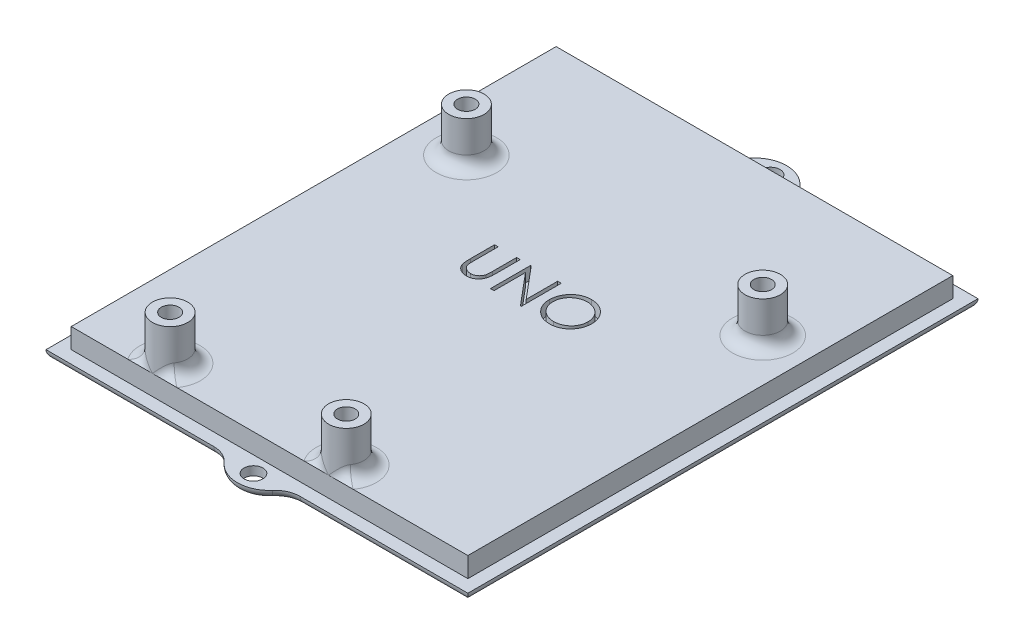
SolidWorks part; units mm, degrees
ref_plane "Front Plane" through (0, 0, 0) normal (0, 0, 1) x (1, 0, 0)
ref_plane "Top Plane" through (0, 0, 0) normal (0, 1, 0) x (1, 0, 0)
ref_plane "Right Plane" through (0, 0, 0) normal (1, 0, 0) x (0, 0, -1)
sketch "Sketch1" plane through (0, 0, 0) normal (0, 1, 0) x (1, 0, 0)
  line L0 (-31.45, 38.45) -> (31.45, 38.45)
  line L5 (-31.45, 38.45) -> (-31.45, -38.45)
  line L6 (-31.45, -38.45) -> (31.45, -38.45)
  line L7 (31.45, 38.45) -> (31.45, -38.45)
  point P11 (-31.45, 0)
  point P12 (0, -38.45)
  dimension "D3" = 76.9
  dimension "D4" = 62.9
extrude "Boss-Extrude1" add sketch "Sketch1" along normal blind 4.575
sketch "Sketch2" plane through (0, 4.575, 0) normal (0, 1, 0) x (1, 0, 0)
  line L0 (9.37, -35.65) -> (9.37, 15.15) construction
  line L1 (24.61, 15.15) -> (9.37, 15.15) construction
  line L2 (9.37, -35.65) -> (-18.57, -35.65) construction
  line L3 (-18.57, -35.65) -> (-18.57, 16.42) construction
  line L4 (0, -38.45) -> (0, 38.45) construction
  line L5 (-31.45, 0) -> (31.45, 0) construction
  line L6 (-18.57, 16.42) -> (-23.65, 16.42) construction
  line L11 (-31.45, 38.45) -> (-31.45, -38.45) construction
  line L12 (-31.45, -38.45) -> (31.45, -38.45) construction
  line L13 (31.45, 38.45) -> (-31.45, 38.45) construction
  line L14 (31.45, -38.45) -> (31.45, 38.45) construction
  circle A0 centre (9.37, -35.65) radius 2.8
  circle A1 centre (24.61, 15.15) radius 2.8
  circle A2 centre (-23.65, 16.42) radius 2.8
  circle A3 centre (-18.57, -35.65) radius 2.8
  circle A4 centre (24.61, 15.15) radius 1.4
  circle A5 centre (9.37, -35.65) radius 1.4
  circle A6 centre (-18.57, -35.65) radius 1.4
  circle A7 centre (-23.65, 16.42) radius 1.4
  dimension "D7" = 2.8
  dimension "D10" = 1.4
  dimension "D6" = 7.8
  dimension "D1" = 27.94
  dimension "D2" = 15.24
  dimension "D3" = 5.08
  dimension "D4" = 1.27
  dimension "D5" = 50.8
extrude "Boss-Extrude2" add sketch "Sketch2" along normal blind 7
sketch "Sketch3" plane through (0, 4.575, 0) normal (0, 1, 0) x (1, 0, 0)
  circle A0 centre (9.37, -35.65) radius 1.4
  circle A1 centre (-18.57, -35.65) radius 1.4
  circle A2 centre (-23.65, 16.42) radius 1.4
  circle A3 centre (24.61, 15.15) radius 1.4
  circle A4 centre (24.61, 15.15) radius 1.4 construction
  circle A5 centre (-23.65, 16.42) radius 1.4 construction
extrude "Cut-Extrude1" cut sketch "Sketch3" against normal offset from surface (3.575 mm away) 1 up to face at (0, 0, 0)
sketch "Sketch7" plane through (0, 0, 0) normal (0, -1, 0) x (1, 0, 0)
  line L8 (-33.45, 40.45) -> (-33.45, -40.45)
  line L9 (-33.45, -40.45) -> (33.45, -40.45)
  line L10 (33.45, -40.45) -> (33.45, 40.45)
  line L11 (33.45, 40.45) -> (-33.45, 40.45)
  line L12 (-33.45, 40.45) -> (-33.45, -40.45)
  line L13 (-33.45, -40.45) -> (33.45, -40.45)
  line L14 (33.45, -40.45) -> (33.45, 40.45)
  line L15 (33.45, 40.45) -> (-33.45, 40.45)
  dimension "D1" = 2
extrude "Boss-Extrude5" add sketch "Sketch7" against normal blind 1.4
sketch "Sketch4" plane through (0, 0, 0) normal (0, 1, 0) x (1, 0, 0)
  line L2 (-6.8418, -40.45) -> (6.8418, -40.45)
  line L3 (-31.45, -38.45) -> (31.45, -38.45) construction
  line L6 (-18.57, -38.45) -> (9.37, -38.45) construction
  line L7 (33.45, -40.45) -> (-33.45, -40.45) construction
  arc A3 (-6.8418, -40.45) -> (-3.8344, -41.8126) centre (-6.8418, -44.45) cw
  arc A4 (-3.8344, -41.8126) -> (3.8344, -41.8126) centre (0, -38.45) ccw
  arc A5 (3.8344, -41.8126) -> (6.8418, -40.45) centre (6.8418, -44.45) cw
  point P6 (0, -38.45)
  dimension "D1" = 5.1
  dimension "D2" = 4
extrude "Boss-Extrude3" add sketch "Sketch4" along normal blind 1.4
sketch "Sketch8" plane through (0, 1.4, 0) normal (0, 1, 0) x (1, 0, 0)
  line L0 (0, -38.45) -> (0, -43.55) construction
  line L1 (31.45, -38.45) -> (-31.45, -38.45) construction
  arc A0 (-3.8344, -41.8126) -> (3.8344, -41.8126) centre (0, -38.45) ccw construction
  circle A1 centre (0, -41) radius 1.5
  dimension "D1" = 3
extrude "Cut-Extrude3" cut sketch "Sketch8" against normal up to next
mirror "Mirror1" about plane through (0, 0, 0) normal (0, 0, 1) of "Cut-Extrude3", "Boss-Extrude3"
sketch "Sketch5" plane through (0, 4.575, 0) normal (0, 1, 0) x (1, 0, 0)
  line L0 (-15, 0) -> (15, 0) construction
  text T0 "UNO" font "Century Gothic" height in points 24
  point P6 (0, 0)
  dimension "D1" = 30
extrude "Cut-Extrude2" cut sketch "Sketch5" against normal blind 2
fillet "Fillet1" radius 1.4 12 edges at (20.1459, 0, -40.45) (5.1909, 0, -40.8066) (0, 0, -43.55) (-5.1909, 0, -40.8066) (-20.1459, 0, -40.45) (-33.45, 0, 0) (-20.1459, 0, 40.45) (-5.1909, 0, 40.8066) (0, 0, 43.55) (5.1909, 0, 40.8066) (20.1459, 0, 40.45) (33.45, 0, 0)
fillet "Fillet2" radius 2 4 edges at (24.61, 4.575, -12.35) (-23.65, 4.575, -13.62) (9.37, 4.575, 38.45) (-18.57, 4.575, 38.45)
